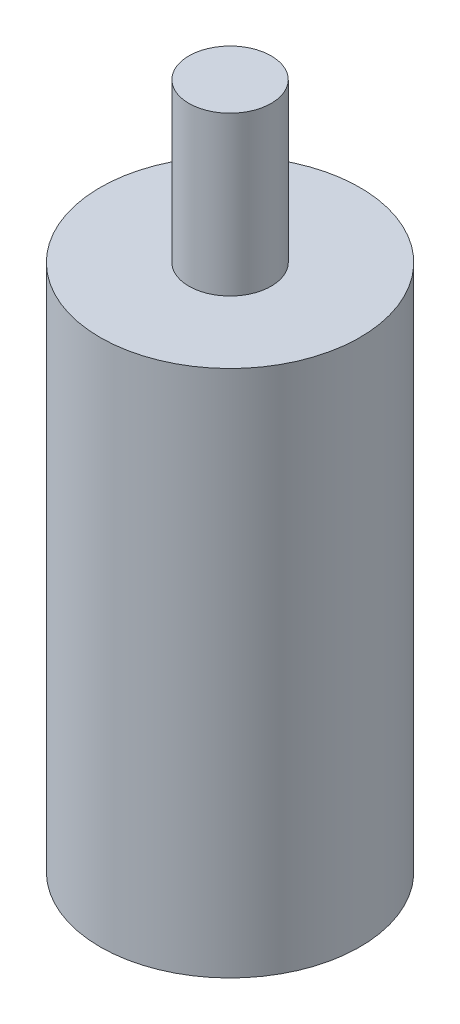
SolidWorks part; units mm, degrees
ref_plane "Front Plane" through (0, 0, 0) normal (0, 0, 1) x (1, 0, 0)
ref_plane "Top Plane" through (0, 0, 0) normal (0, 1, 0) x (1, 0, 0)
ref_plane "Right Plane" through (0, 0, 0) normal (1, 0, 0) x (0, 0, -1)
sketch "Sketch1" plane through (0, 0, 0) normal (0, 1, 0) x (1, 0, 0)
  circle A0 centre (2.052, 1.3593) radius 2.4614
  circle A1 centre (2.052, 1.3593) radius 0.78
  dimension "D1" = 4.9227
  dimension "D2" = 1.56
extrude "Boss-Extrude2" add sketch "Sketch1" along normal blind 3 contours A1 | A1 region at (2.052, 0, -1.3593)
extrude "Boss-Extrude3" add sketch "Sketch1<5>" against normal blind 10 separate body
sketch "Sketch1<5>" plane through (0, 0, 0) normal (0, 1, 0) x (1, 0, 0) same geometry as "Sketch1"
